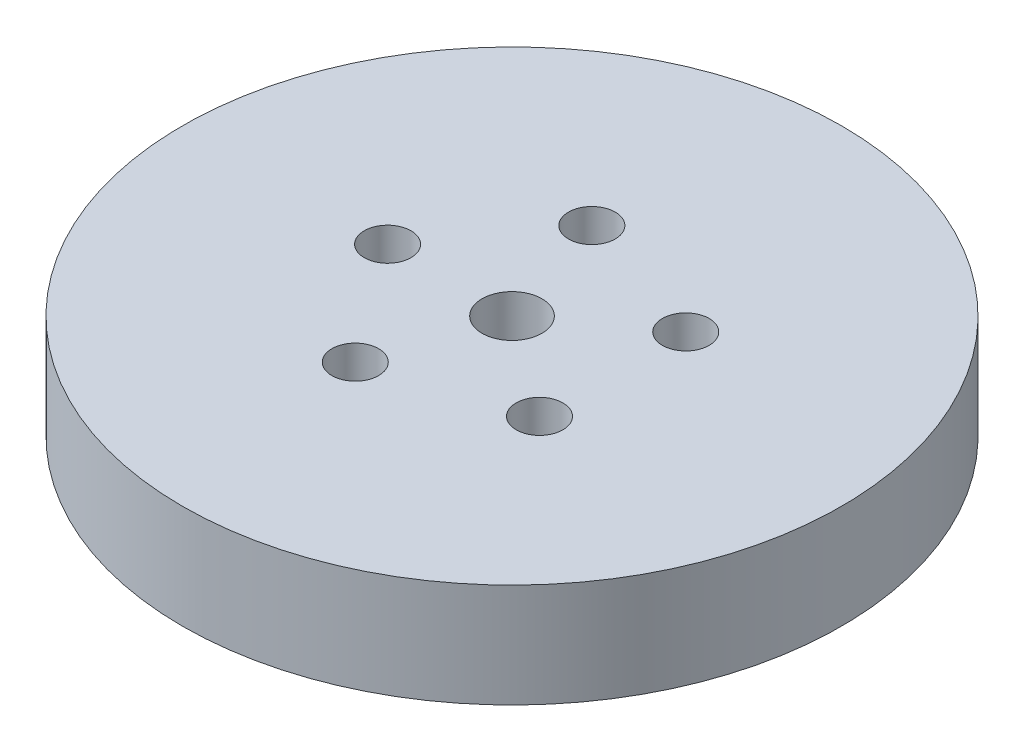
SolidWorks part; units mm, degrees
ref_plane "Front Plane" through (0, 0, 0) normal (0, 0, 1) x (1, 0, 0)
ref_plane "Top Plane" through (0, 0, 0) normal (0, 1, 0) x (1, 0, 0)
ref_plane "Right Plane" through (0, 0, 0) normal (1, 0, 0) x (0, 0, -1)
sketch "Sketch1" plane through (0, 0, 0) normal (0, 1, 0) x (1, 0, 0)
  circle A0 centre (0, 0) radius 82.5
  dimension "FLANGE_OD" = 165
extrude "Boss-Extrude1" add sketch "Sketch1" along normal blind 26
sketch "Sketch2" plane through (0, 0, 0) normal (0, 1, 0) x (1, 0, 0)
  circle A0 centre (0, 0) radius 7.5
  dimension "BORE_D" = 15
extrude "Cut-Extrude1" cut sketch "Sketch2" along normal through all
sketch "Sketch3" plane through (0, 26, 0) normal (0, 1, 0) x (1, 0, 0)
  circle A0 centre (0, 0) radius 31.1386 construction
  circle A1 centre (-31.1386, 0) radius 5.8483
  dimension "BOLT_D" = 11.6967
  dimension "BOLT_PCD" = 62.2772
extrude "Cut-Extrude2" cut sketch "Sketch3" against normal blind 21.1991
pattern_circular "CirPattern1" count 5 over 360 about axis through (0, 0, 0) along (0, 1, 0) of "Cut-Extrude2"
